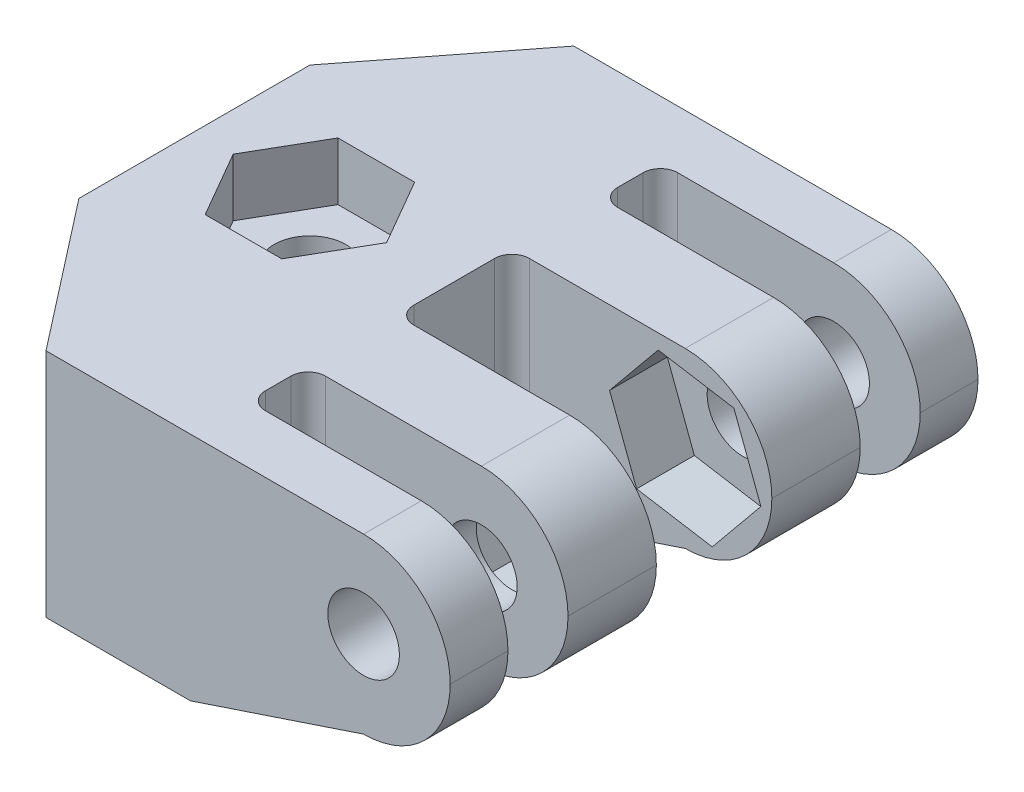
SolidWorks part; units mm, degrees
material "Ceramic Porcelain"
ref_plane "Front Plane" through (0, 0, 0) normal (0, 0, 1) x (1, 0, 0)
ref_plane "Top Plane" through (0, 0, 0) normal (0, 1, 0) x (1, 0, 0)
ref_plane "Right Plane" through (0, 0, 0) normal (1, 0, 0) x (0, 0, -1)
sketch "Sketch1" plane through (0, 0, 0) normal (0, 1, 0) x (1, 0, 0)
  line L0 (0, 0) -> (-35, 0)
  line L1 (-35, 0) -> (-45, 12.85)
  line L2 (-45, 12.85) -> (-45, 32.85)
  line L3 (-45, 32.85) -> (-35, 45.7)
  line L4 (-35, 45.7) -> (0, 45.7)
  line L5 (0, 45.7) -> (0, 40.7)
  line L6 (0, 40.7) -> (-22.5, 40.7)
  line L7 (-22.5, 40.7) -> (-22.5, 35.5)
  line L8 (-22.5, 35.5) -> (0, 35.5)
  line L9 (0, 35.5) -> (0, 27.85)
  line L10 (0, 10.2) -> (-22.5, 10.2)
  line L11 (-22.5, 10.2) -> (-22.5, 5)
  line L12 (-22.5, 5) -> (0, 5)
  line L13 (0, 5) -> (0, 0)
  line L14 (0, 17.85) -> (0, 10.2)
  line L15 (0, 27.85) -> (-22.5, 27.85)
  line L17 (0, 17.85) -> (-22.5, 17.85)
  line L18 (-22.5, 27.85) -> (-22.5, 17.85)
  dimension "D1" = 5.2
  dimension "D2" = 5
  dimension "D3" = 25.3
  dimension "D4" = 35
  dimension "D5" = 20
  dimension "D6" = 45
  dimension "D7" = 22.5
  dimension "D8" = 10
extrude "Boss-Extrude1" add sketch "Sketch1" along normal blind 15
sketch "Sketch5" plane through (0, 15, 0) normal (0, 1, 0) x (1, 0, 0)
  line L0 (-45, 32.85) -> (-45, 22.85) construction
  line L1 (-41.6395, 22.85) -> (-38.3198, 17.1)
  line L2 (-38.3198, 17.1) -> (-31.6802, 17.1)
  line L3 (-31.6802, 17.1) -> (-28.3605, 22.85)
  line L4 (-28.3605, 22.85) -> (-31.6802, 28.6)
  line L5 (-31.6802, 28.6) -> (-38.3198, 28.6)
  line L6 (-38.3198, 28.6) -> (-41.6395, 22.85)
  line L7 (-45, 32.85) -> (-45, 12.85) construction
  circle A0 centre (-35, 22.85) radius 5.75 construction
  dimension "D1" = 11.5
  dimension "D2" = 10
extrude "Cut-Extrude4" cut sketch "Sketch5" against normal blind 5 contours L5 L6 L1 L2 L3 L4
sketch "Sketch7" plane through (0, 0, 0) normal (0, 0, 1) x (1, 0, 0)
  line L0 (-35, 15) -> (0, 15) construction
  line L1 (0, 15) -> (0, 0) construction
  circle A0 centre (-7.5, 7.5) radius 3.1
  dimension "D1" = 6.2
  dimension "D2" = 7.5
  dimension "D3" = 7.5
extrude "Cut-Extrude6" cut sketch "Sketch7" against normal through all
fillet "Fillet1" radius 7.5 8 edges at (0, 0, -43.2) (0, 0, -31.675) (0, 0, -2.5) (0, 15, -43.2) (0, 15, -31.675) (0, 15, -2.5) (0, 0, -14.025) (0, 15, -14.025)
sketch "Sketch8" plane through (0, 0, -27.85) normal (0, 0, 1) x (1, 0, 0)
  line L1 (-9.8396, 13.7136) -> (-14.051, 8.5806)
  line L2 (-14.051, 8.5806) -> (-11.7114, 2.367)
  line L3 (-11.7114, 2.367) -> (-5.1604, 1.2864)
  line L4 (-5.1604, 1.2864) -> (-0.949, 6.4194)
  line L5 (-0.949, 6.4194) -> (-3.2886, 12.633)
  line L6 (-3.2886, 12.633) -> (-9.8396, 13.7136)
  circle A0 centre (-7.5, 7.5) radius 5.75 construction
  dimension "D1" = 11.5
extrude "Cut-Extrude7" cut sketch "Sketch8" against normal blind 5
sketch "Sketch9" plane through (0, 0, -17.85) normal (0, 0, -1) x (-1, 0, 0)
  line L1 (9.8396, 13.7136) -> (3.2886, 12.633)
  line L2 (3.2886, 12.633) -> (0.949, 6.4194)
  line L3 (0.949, 6.4194) -> (5.1604, 1.2864)
  line L4 (5.1604, 1.2864) -> (11.7114, 2.367)
  line L5 (11.7114, 2.367) -> (14.051, 8.5806)
  line L6 (14.051, 8.5806) -> (9.8396, 13.7136)
  circle A0 centre (7.5, 7.5) radius 5.75 construction
  dimension "D1" = 11.5
extrude "Cut-Extrude8" cut sketch "Sketch9" against normal blind 5
fillet "Fillet2" radius 1.5 6 edges at (-22.5, 7.5, -40.7) (-22.5, 7.5, -35.5) (-22.5, 7.5, -27.85) (-22.5, 7.5, -17.85) (-22.5, 7.5, -10.2) (-22.5, 7.5, -5)
sketch "Sketch11" [suppressed] plane through (0, 0, 0) normal (0, 0, 1) x (1, 0, 0)
  line L1 (-45, 15) -> (-25, 15)
  line L2 (-45, 15) -> (-45, 10)
  line L3 (-45, 10) -> (-25, 10)
  line L4 (-25, 15) -> (-25, 10)
  dimension "D1" = 5
  dimension "D2" = 20
extrude "Cut-Extrude9" [suppressed] cut sketch "Sketch11" against normal through all
chamfer "Chamfer1" [suppressed] distance 5 angle 45
ref_plane "Plane1" [suppressed] through (-35, 0, 0) normal (-1, 0, 0) x (0, 0, 1)
sketch "Sketch12" [suppressed] plane through (-35, 0, 0) normal (-1, 0, 0) x (0, 0, 1)
  line L0 (-22.85, 14.0184) -> (-22.85, -3.9816)
  arc A0 (-22.85, 14.0184) -> (-22.85, -3.9816) centre (-22.85, 5.0184) ccw
  dimension "D1" = 9
  dimension "D2" = 22.85
  dimension "D3" = 5.0184
revolve "Cut-Revolve3" [suppressed] cut sketch "Sketch12" angle 360 about L0
chamfer "Chamfer6" [suppressed] distance 1 angle 60
sketch "Sketch13" [suppressed] plane through (-45, 0, 0) normal (-1, 0, 0) x (0, 0, 1)
  line L1 (-45.7, 10) -> (0, 10)
  line L2 (-45.7, 10) -> (-45.7, 0)
  line L3 (-45.7, 0) -> (0, 0)
  line L4 (0, 10) -> (0, 0)
extrude "Cut-Extrude10" [suppressed] cut sketch "Sketch13" against normal blind 10
sketch "Sketch14" [suppressed] plane through (-35, 0, 0) normal (-1, 0, 0) x (0, 0, 1)
  line L0 (-45.7, 0) -> (-31.2854, 0) construction
  line L1 (-45.7, 10) -> (-45.7, 0) construction
  line L2 (0, 10) -> (0, 0) construction
  circle A0 centre (-39.2, 5) radius 4
  circle A1 centre (-6.5, 5) radius 4
  dimension "D1" = 8
  dimension "D2" = 5
  dimension "D3" = 6.5
  dimension "D4" = 6.5
extrude "Cut-Extrude11" [suppressed] cut sketch "Sketch14" against normal blind 10
chamfer "Chamfer7" [suppressed] distance 1 angle 45
sketch "Sketch15" plane through (0, 0, 0) normal (0, -1, 0) x (1, 0, 0)
  line L0 (-35, 0) -> (-45, -12.85)
  line L1 (-45, -12.85) -> (-45, -32.85)
  line L2 (-45, -32.85) -> (-35, -45.7)
  line L3 (-7.5, -45.7) -> (-35, -45.7) construction
  line L4 (-35, -45.7) -> (-22.5, -45.7)
  line L5 (-22.5, -45.7) -> (-22.5, 0)
  line L6 (-35, 0) -> (-7.5, 0) construction
  line L7 (-22.5, 0) -> (-35, 0)
  line L8 (-35, -45.7) -> (-45, -32.85) construction
  dimension "D1" = 12.5
extrude "Boss-Extrude2" add sketch "Sketch15" along normal blind 5
sketch "Sketch6" plane through (0, 10, 0) normal (0, 1, 0) x (1, 0, 0)
  circle A0 centre (-35, 22.85) radius 3.1
  dimension "D1" = 6.2
extrude "Cut-Extrude5" cut sketch "Sketch6" against normal through all
chamfer "Chamfer8" distance 15 distance2 5 4 edges at (-22.5, 0, -3.25) (-22.5, 0, -42.45) (-22.5, 0, -14.025) (-22.5, 0, -31.675) first distance on face at (-16.2621, 0, -3.2379) first distance on face at (-16.2621, 0, -42.4621) first distance on face at (-17.1036, 0, -14.025) first distance on face at (-17.1036, 0, -31.675)
